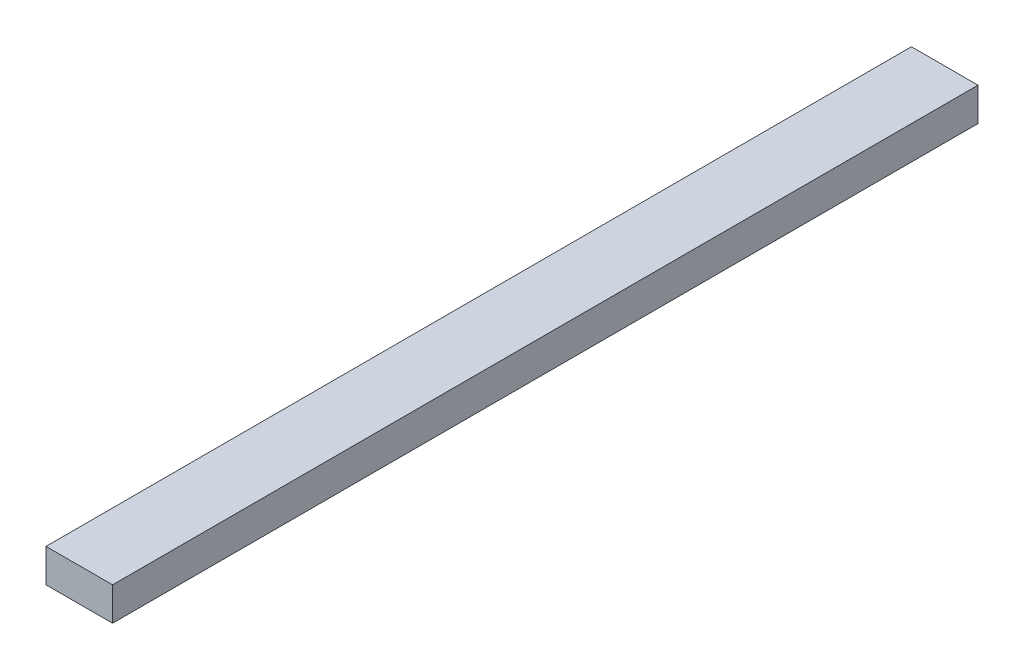
SolidWorks part; units mm, degrees
ref_plane "Front Plane" through (0, 0, 0) normal (0, 0, 1) x (1, 0, 0)
ref_plane "Top Plane" through (0, 0, 0) normal (0, 1, 0) x (1, 0, 0)
ref_plane "Right Plane" through (0, 0, 0) normal (1, 0, 0) x (0, 0, -1)
sketch "Sketch1" plane through (0, 0, 0) normal (0, 0, 1) x (1, 0, 0)
  line L1 (0, 0) -> (50.8, 0)
  line L2 (0, 0) -> (0, 25.4)
  line L3 (0, 25.4) -> (50.8, 25.4)
  line L4 (50.8, 0) -> (50.8, 25.4)
  dimension "D1" = 25.4
  dimension "D2" = 50.8
extrude "Boss-Extrude1" add sketch "Sketch1" along normal blind 660.4
